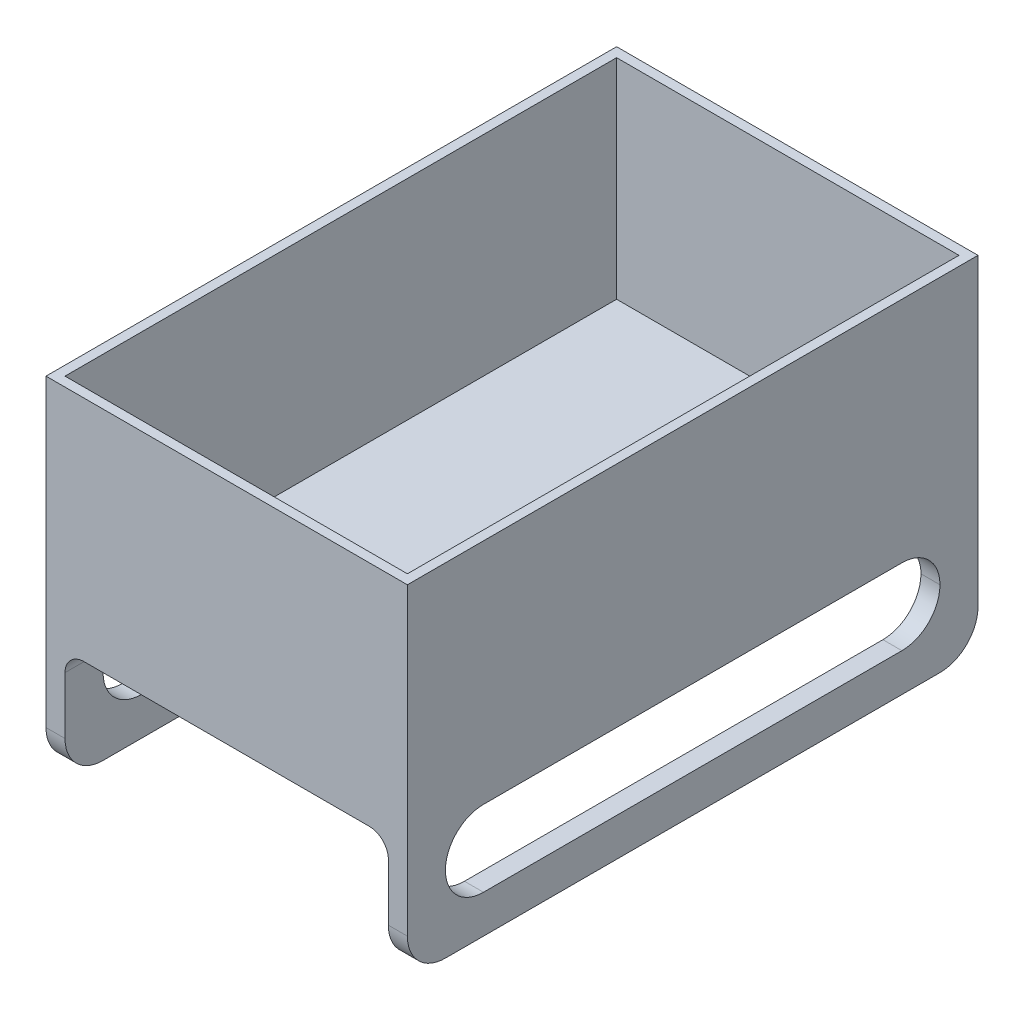
SolidWorks part; units mm, degrees
material "Nylon 101"
ref_plane "Front" through (0, 0, 0) normal (0, 0, 1) x (1, 0, 0)
ref_plane "Top" through (0, 0, 0) normal (0, 1, 0) x (1, 0, 0)
ref_plane "Right" through (0, 0, 0) normal (1, 0, 0) x (0, 0, -1)
sketch "Sketch1" plane through (0, 0, 0) normal (0, 0, 1) x (1, 0, 0)
  line L0 (0, 0) -> (0, 26.6214) construction
  line L1 (-47.5, 0) -> (47.5, 0)
  line L2 (-47.5, 0) -> (-47.5, 90)
  line L3 (-47.5, 90) -> (47.5, 90)
  line L4 (47.5, 0) -> (47.5, 90)
  line L6 (-42.5, 0) -> (42.5, 0)
  line L7 (-42.5, 0) -> (-42.5, 30)
  line L8 (-42.5, 30) -> (42.5, 30)
  line L9 (42.5, 0) -> (42.5, 30)
  dimension "D1" = 30
  dimension "D2" = 85
  dimension "D3" = 95
  dimension "D4" = 90
extrude "Boss-Extrude1" add sketch "Sketch1" against normal blind 150 contours L9 L1 L4 L3 L2 L7 L8 region at (0, 57.75, 0)
fillet "Fillet1" radius 10 4 edges at (-45, 0, -150) (45, 0, -150) (45, 0, 0) (-45, 0, 0)
sketch "Sketch2" plane through (47.5, 0, 0) normal (1, 0, 0) x (0, 0, -1)
  line L0 (150, 30) -> (0, 30) construction
  line L5 (150, 30) -> (0, 30)
  line L14 (10, 10) -> (140, 10)
  line L15 (140, 10) -> (140, 80)
  line L16 (140, 80) -> (10, 80)
  line L17 (10, 80) -> (10, 10)
  line L18 (20, 10) -> (130, 10)
  line L19 (140, 20) -> (140, 30)
  line L21 (10, 30) -> (10, 20)
  arc A2 (140, 20) -> (130, 10) centre (130, 20) cw
  arc A3 (20, 10) -> (10, 20) centre (20, 20) cw
  point P4 (0, 0)
  point P7 (14.0641, 30)
  point P8 (-14.1118, 30)
  dimension "D2" = 10
  dimension "D1" = 10
extrude "Cut-Extrude1" cut sketch "Sketch2" against normal through all contours A3 L18 A2 L19 L5 L21 region at (47.5, 20.1304, -75)
fillet "Fillet2" radius 10 4 edges at (-45, 30, -140) (-45, 30, -10) (45, 30, -140) (45, 30, -10)
sketch "Sketch3" plane through (0, 90, 0) normal (0, 1, 0) x (1, 0, 0)
  line L8 (-45, 2.5) -> (45, 2.5)
  line L9 (45, 2.5) -> (45, 147.5)
  line L10 (45, 147.5) -> (-45, 147.5)
  line L11 (-45, 147.5) -> (-45, 2.5)
  line L12 (-45, 2.5) -> (45, 2.5)
  line L13 (45, 2.5) -> (45, 147.5)
  line L14 (45, 147.5) -> (-45, 147.5)
  line L15 (-45, 147.5) -> (-45, 2.5)
  dimension "D1" = 2.5
extrude "Cut-Extrude2" cut sketch "Sketch3" against normal offset from surface (55 mm away) 5 contours L14 L15 L12 L13 region at (0, 90, -75) up to face at (0, 30, -75)
fillet "Fillet3" radius 5 4 edges at (42.5, 30, -10) (42.5, 30, -140) (-42.5, 30, -140) (-42.5, 30, -10)
